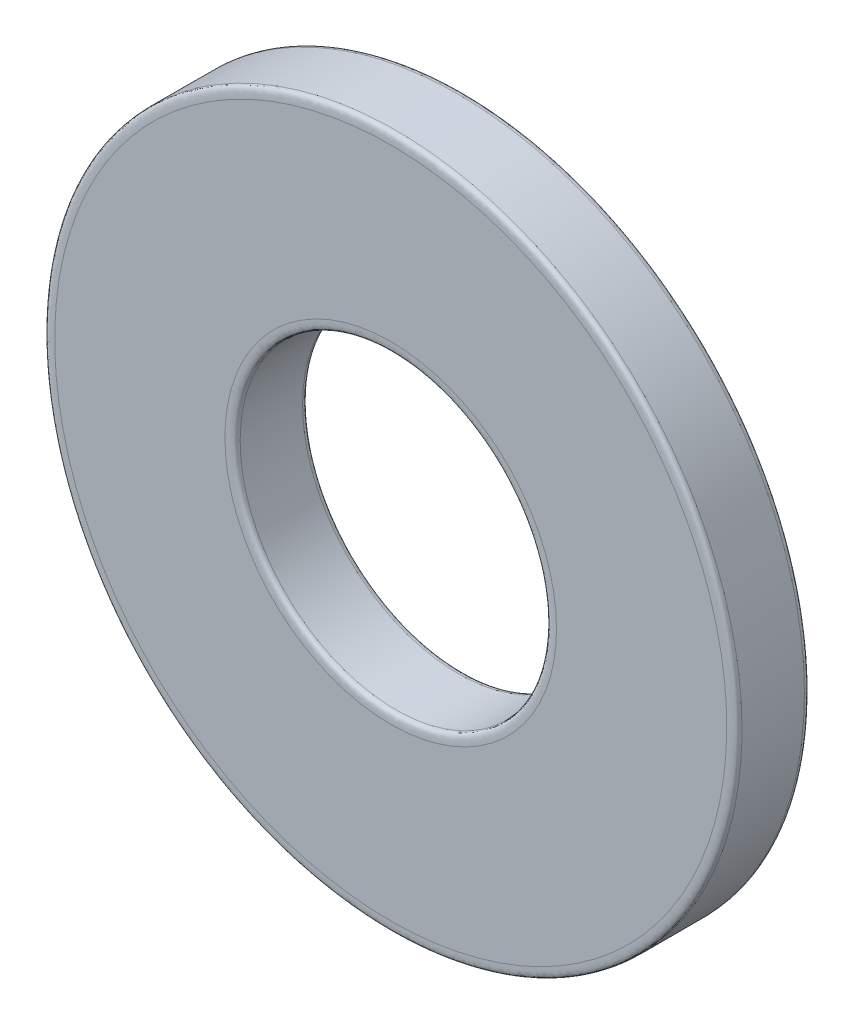
SolidWorks part; units mm, degrees
material "Alloy Steel (SS)"
ref_plane "Front Plane" through (0, 0, 0) normal (0, 0, 1) x (1, 0, 0)
ref_plane "Top Plane" through (0, 0, 0) normal (0, 1, 0) x (1, 0, 0)
ref_plane "Right Plane" through (0, 0, 0) normal (1, 0, 0) x (0, 0, -1)
sketch "Sketch1" plane through (0, 0, 0) normal (0, 0, 1) x (1, 0, 0)
  circle A0 centre (0, 0) radius 3.5687
  circle A1 centre (0, 0) radius 7.9375
  point P4 (0, -3.5687)
  dimension "ID" = 7.1374
  dimension "OD" = 15.875
sketch "Sketch2" plane through (0, 0, 0) normal (1, 0, 0) x (0, 0, -1)
  line L0 (-0.8319, -7.9375) -> (0.8318, -7.9375) construction
  point P2 (0, -7.9375)
  dimension "Thickness Range" = 1.6637
sketch "Sketch3" plane through (0, 0, 0) normal (0, 0, 1) x (1, 0, 0)
  circle A0 centre (0, 0) radius 3.5687 construction
  circle A1 centre (0, 0) radius 7.9375 construction
  circle A2 centre (0, 0) radius 3.5687
  circle A3 centre (0, 0) radius 7.9375
extrude "Boss-Extrude1" add sketch "Sketch3" along normal mid plane 1.6637
fillet "Fillet1" radius 0.2329 4 edges at (7.9375, 0, -0.8318) (3.5687, 0, -0.8318) (7.9375, 0, 0.8318) (3.5687, 0, 0.8318)
equation "\"D1@Boss-Extrude1\" = \"Thickness Range@Sketch2\""
equation "\"D2@Fillet1\"=\"Thickness Range@Sketch2\"*0.07"
equation "\"D1@Fillet1\"=\"D2@Fillet1\"*2"
